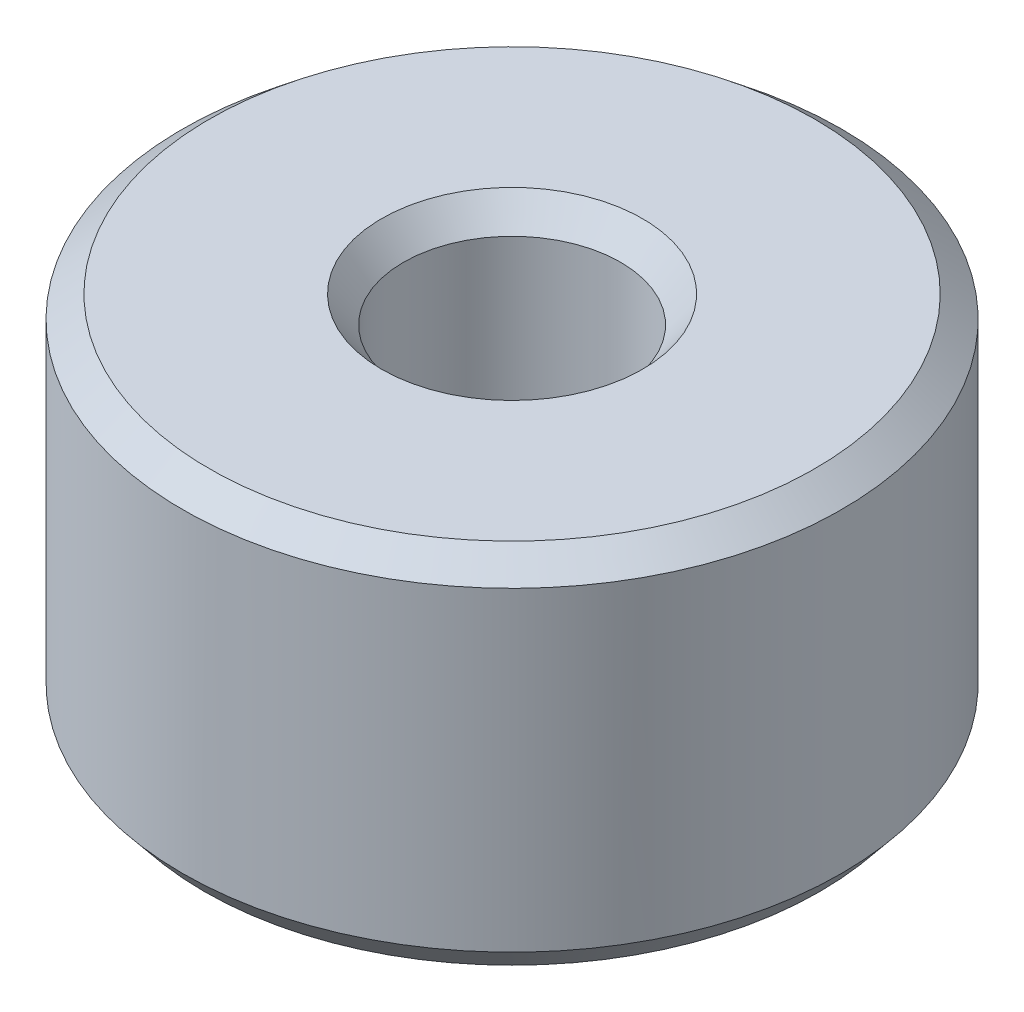
SolidWorks part; units mm, degrees
ref_plane "Front Plane" through (0, 0, 0) normal (0, 0, 1) x (1, 0, 0)
ref_plane "Top Plane" through (0, 0, 0) normal (0, 1, 0) x (1, 0, 0)
ref_plane "Right Plane" through (0, 0, 0) normal (1, 0, 0) x (0, 0, -1)
sketch "Sketch1" plane through (0, 0, 0) normal (0, 1, 0) x (1, 0, 0)
  circle A0 centre (0, 0) radius 5
  dimension "SLEEVE_OD" = 10
extrude "Boss-Extrude1" add sketch "Sketch1" along normal blind 5.5202
sketch "Sketch2" plane through (0, 0, 0) normal (0, 1, 0) x (1, 0, 0)
  circle A0 centre (0, 0) radius 1.6471
  dimension "BORE_D" = 3.2942
extrude "Cut-Extrude1" cut sketch "Sketch2" along normal through all
chamfer "Chamfer1" distance 0.333 angle 50.692 4 edges at (0, 5.5202, 1.6471) (0, 0, 1.6471) (0, 0, 5) (0, 5.5202, 5) first distance on face at (0, 5.5202, 1.6471) first distance on face at (0, 0, 1.6471) first distance on face at (0, 5.5202, 5)
